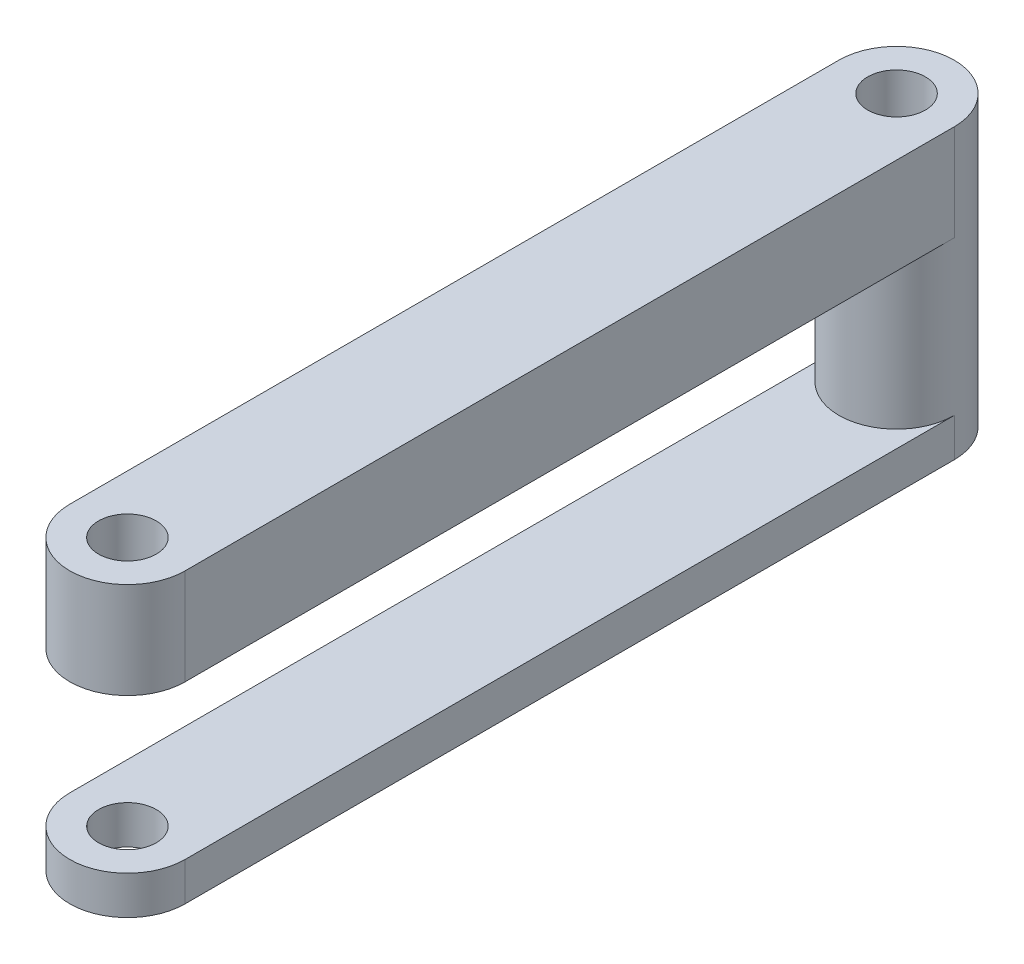
SolidWorks part; units mm, degrees
material "ABS"
ref_plane "Front Plane" through (0, 0, 0) normal (0, 0, 1) x (1, 0, 0)
ref_plane "Top Plane" through (0, 0, 0) normal (0, 1, 0) x (1, 0, 0)
ref_plane "Right Plane" through (0, 0, 0) normal (1, 0, 0) x (0, 0, -1)
sketch "Sketch1" plane through (0, 0, 0) normal (0, 1, 0) x (1, 0, 0)
  line L0 (0, 0) -> (0, -40) construction
  line L1 (3, 0) -> (3, -40)
  line L2 (-3, 0) -> (-3, -40)
  arc A0 (3, 0) -> (-3, 0) centre (0, 0) ccw
  arc A1 (-3, -40) -> (3, -40) centre (0, -40) ccw
  point P3 (0, -20)
  dimension "D2" = 3
  dimension "D1" = 40
extrude "Boss-Extrude1" add sketch "Sketch1" along normal blind 2 contours L1 A1 L2 A0
sketch "Sketch2" plane through (0, 2, 0) normal (0, 1, 0) x (1, 0, 0)
  circle A0 centre (0, 0) radius 3
  dimension "D1" = 6
extrude "Boss-Extrude2" add sketch "Sketch2" along normal blind 12
extrude "Boss-Extrude3" add sketch "Sketch1<3>" along normal blind 5 from offset 10
sketch "Sketch1<3>" plane through (0, 0, 0) normal (0, 1, 0) x (1, 0, 0) same geometry as "Sketch1"
hole_wizard "Ø3.0mm Clearance Dowel Hole1" positions "Sketch3" profile "Sketch4" hole size "Ø3.0" standard "ANSI Metric" end condition through all
sketch "Sketch3" plane through (0, 15, 0) normal (0, 1, 0) x (1, 0, 0)
  point P0 (0, 0)
  point P3 (0, -40)
sketch "Sketch4" plane through (0, 15, 0) normal (1, 0, 0) x (0, 0, 1)
  line L0 (0, 0) -> (0, 15)
  line L1 (0, 15) -> (1.5, 15)
  line L2 (1.5, 15) -> (1.5, 0)
  line L5 (1.5, 0) -> (0, 0)
  line L11 (0, -6.35) -> (0, 107.95) construction
  dimension "Thru Hole Dia." = 3
  dimension "Thru Hole Depth" = 15
